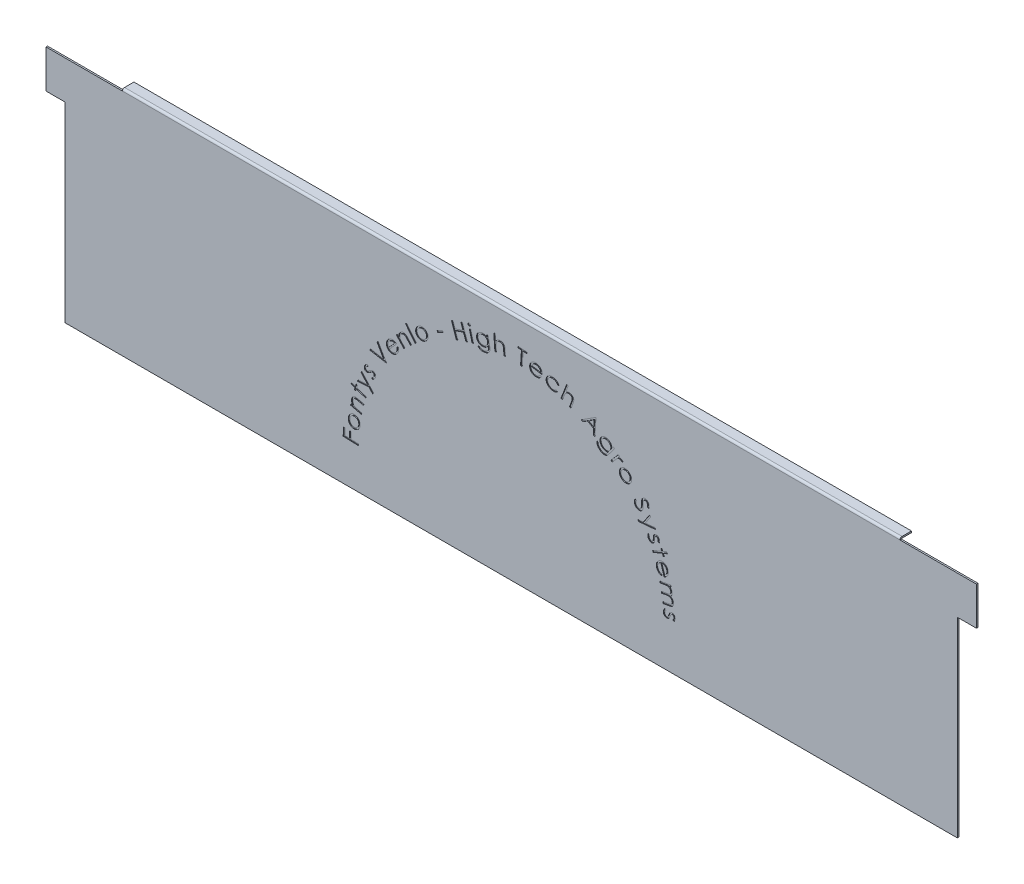
SolidWorks part; units mm, degrees
note: The reader was unsure of these and kept them because the rebuilt part matched: flange length of "Edge-Flange1".
material "1060 Alloy"
ref_plane "Front Plane" through (0, 0, 0) normal (0, 0, 1) x (1, 0, 0)
ref_plane "Top Plane" through (0, 0, 0) normal (0, 1, 0) x (1, 0, 0)
ref_plane "Right Plane" through (0, 0, 0) normal (1, 0, 0) x (0, 0, -1)
sketch "Sketch1" plane through (0, 0, 0) normal (0, 0, 1) x (1, 0, 0)
  line L0 (960.4168, 91.4559) -> (985.4168, 91.4559)
  line L1 (-231.5832, 141.4559) -> (985.4168, 141.4559)
  line L2 (-231.5832, 141.4559) -> (-231.5832, 91.4559)
  line L3 (-231.5832, 91.4559) -> (-206.5832, 91.4559)
  line L4 (985.4168, 141.4559) -> (985.4168, 91.4559)
  line L6 (-206.5832, 91.4559) -> (-206.5832, -158.5441)
  line L7 (-206.5832, -158.5441) -> (960.4168, -158.5441)
  line L8 (960.4168, 91.4559) -> (960.4168, -158.5441)
  dimension "D1" = 1217
  dimension "D2" = 50
  dimension "D3" = 250
  dimension "D4" = 25
  dimension "D5" = 25
base flange "Base-Flange1" sketch "Sketch1" thickness 2 reverse thickness direction no parameters "D1"=0.7366
edge flange "Edge-Flange1" sketch "Sketch5" flange angle 90 flange length 15 flange position bend outside bend radius 0.7366 thickness 2 relief rectangular parameters "D6"=10
sketch "Sketch5" plane through (0, 141.4559, -2) normal (0, 1, 0) x (1, 0, 0)
  line L2 (-131.5832, 0) -> (-131.5832, 13)
  line L3 (-131.5832, 13) -> (885.4168, 13)
  line L4 (885.4168, 13) -> (885.4168, 0)
  line L7 (985.4168, 0) -> (-231.5832, 0) construction
  line L8 (885.4168, 0) -> (-131.5832, 0)
  line L11 (-231.5832, 0) -> (-231.5832, -2) construction
  line L12 (985.4168, 0) -> (985.4168, -2) construction
  dimension "D1" = 100
  dimension "D2" = 100
bend "EdgeBend1" bend radius 0.7366 bend angle 90 parameters "D5"=1
sketch "Sketch6" plane through (0, 0, 0) normal (0, 0, 1) x (1, 0, 0)
  line L4 (885.4168, 141.4559) -> (-131.5832, 141.4559) construction
  line L5 (-206.5832, 91.4559) -> (-206.5832, -158.5441) construction
  arc A0 (176.9168, -108.5441) -> (576.9168, -108.5441) centre (376.9168, -108.5441) cw construction
  text T0 "Fontys Venlo - High Tech Agro Systems" font "Century Gothic" height 20
  dimension "D1" = 200
  dimension "D2" = 250
  dimension "D3" = 583.5
extrude "Cut-Extrude1" cut sketch "Sketch6" against normal blind 1
sketch "Bend-Lines1" plane through (0, 0, 0) normal (0, 1, 0) x (1, 0, 0)
sketch "Bounding-Box1" plane through (0, 0, 0) normal (0, 1, 0) x (1, 0, 0)
sheet metal parameters "Sheet-Metal1" thickness 2 parameters "D1"=0.7366
flat pattern "Flat-Pattern1"
sketch "Bend-Lines2" plane through (0, 0, 0) normal (0, 1, 0) x (1, 0, 0)
sketch3d "Bounding-Box2"
  line L0 (-231.5832, -108.5441, 0) -> (985.4168, -108.5441, 0) construction
  line L1 (-231.5832, 141.4559, 0) -> (985.4168, 141.4559, 0) construction
  line L2 (-231.5832, -108.5441, 0) -> (-231.5832, 141.4559, 0) construction
  line L3 (985.4168, -108.5441, 0) -> (985.4168, 141.4559, 0) construction
sheet metal parameters "Sheet-Metal2" thickness 2 parameters "D1"=0.7366
flat pattern "Flat-Pattern1"
sketch "Bend-Lines2" plane through (0, 0, 0) normal (0, 0, 1) x (1, 0, 0)
  line L0 (885.4168, 142.8198) -> (-131.5832, 142.8198) construction
  line L1 (885.4168, 142.8198) -> (-131.5832, 142.8198) construction
sketch3d "Bounding-Box2"
  line L0 (-231.5832, -158.5441, 0) -> (985.4168, -158.5441, 0) construction
  line L1 (-231.5832, 156.4471, 0) -> (985.4168, 156.4471, 0) construction
  line L2 (-231.5832, -158.5441, 0) -> (-231.5832, 156.4471, 0) construction
  line L3 (985.4168, -158.5441, 0) -> (985.4168, 156.4471, 0) construction
bend of the flat pattern "Flatten-<EdgeBend1>1"
sheet metal parameters "Sheet-Metal3" thickness 2 parameters "D1"=0.7366
flat pattern "Flat-Pattern1"
sketch "Bend-Lines2" plane through (0, 0, 0) normal (0, 0, 1) x (1, 0, 0)
  line L0 (885.4168, 142.8198) -> (-131.5832, 142.8198) construction
  line L1 (885.4168, 142.8198) -> (-131.5832, 142.8198) construction
sketch3d "Bounding-Box2"
  line L0 (-231.5832, -158.5441, 0) -> (985.4168, -158.5441, 0) construction
  line L1 (-231.5832, 156.4471, 0) -> (985.4168, 156.4471, 0) construction
  line L2 (-231.5832, -158.5441, 0) -> (-231.5832, 156.4471, 0) construction
  line L3 (985.4168, -158.5441, 0) -> (985.4168, 156.4471, 0) construction
bend of the flat pattern "Flatten-<EdgeBend1>2"
sheet metal parameters "Sheet-Metal4" thickness 2 parameters "D1"=0.7366
flat pattern "Flat-Pattern4"
sketch "Bend-Lines4" plane through (0, 0, 0) normal (0, 1, 0) x (1, 0, 0)
sketch3d "Bounding-Box4" [suppressed]
  line L0 (438.6533, 28.4061, 0) -> (443.5811, 24.4286, 0) construction
  line L1 (435.0553, 23.9484, 0) -> (439.983, 19.9709, 0) construction
  line L2 (438.6533, 28.4061, 0) -> (435.0553, 23.9484, 0) construction
  line L3 (443.5811, 24.4286, 0) -> (439.983, 19.9709, 0) construction
sheet metal parameters "Sheet-Metal5" thickness 2 parameters "D1"=0.7366
flat pattern "Flat-Pattern5"
sketch "Bend-Lines5" plane through (0, 0, 0) normal (0, 1, 0) x (1, 0, 0)
sketch3d "Bounding-Box5" [suppressed]
  line L0 (452.0841, 17.1021, 0) -> (456.1995, 12.4271, 0) construction
  line L1 (447.6628, 13.21, 0) -> (451.7782, 8.5351, 0) construction
  line L2 (452.0841, 17.1021, 0) -> (447.6628, 13.21, 0) construction
  line L3 (456.1995, 12.4271, 0) -> (451.7782, 8.5351, 0) construction
sheet metal parameters "Sheet-Metal6" thickness 2 parameters "D1"=0.7366
flat pattern "Flat-Pattern6"
sketch "Bend-Lines6" plane through (0, 0, 0) normal (0, 1, 0) x (1, 0, 0)
sketch3d "Bounding-Box6" [suppressed]
  line L0 (317.825, 22.7921, 0) -> (322.7823, 26.5097, 0) construction
  line L1 (314.2735, 27.528, 0) -> (319.2308, 31.2456, 0) construction
  line L2 (317.825, 22.7921, 0) -> (314.2735, 27.528, 0) construction
  line L3 (322.7823, 26.5097, 0) -> (319.2308, 31.2456, 0) construction
sheet metal parameters "Sheet-Metal7" thickness 2 parameters "D1"=0.7366
flat pattern "Flat-Pattern7"
sketch "Bend-Lines7" plane through (0, 0, 0) normal (0, 1, 0) x (1, 0, 0)
sketch3d "Bounding-Box7" [suppressed]
  line L0 (276.6653, -48.5354, 0) -> (277.7535, -42.4183, 0) construction
  line L1 (270.8472, -47.5004, 0) -> (271.9355, -41.3833, 0) construction
  line L2 (276.6653, -48.5354, 0) -> (270.8472, -47.5004, 0) construction
  line L3 (277.7535, -42.4183, 0) -> (271.9355, -41.3833, 0) construction
sheet metal parameters "Sheet-Metal8" thickness 2 parameters "D1"=0.7366
flat pattern "Flat-Pattern8"
sketch "Bend-Lines8" plane through (0, 0, 0) normal (0, 1, 0) x (1, 0, 0)
sketch3d "Bounding-Box8" [suppressed]
  line L0 (356.1736, 39.999, 0) -> (362.3149, 41.318, 0) construction
  line L1 (354.9724, 45.5918, 0) -> (361.1136, 46.9109, 0) construction
  line L2 (356.1736, 39.999, 0) -> (354.9724, 45.5918, 0) construction
  line L3 (362.3149, 41.318, 0) -> (361.1136, 46.9109, 0) construction
sheet metal parameters "Sheet-Metal9" thickness 2 parameters "D1"=0.7366
flat pattern "Flat-Pattern9"
sketch "Bend-Lines9" plane through (0, 0, 0) normal (0, 1, 0) x (1, 0, 0)
sketch3d "Bounding-Box9" [suppressed]
  line L0 (296.881, 8.3602, 0) -> (300.8694, 12.7732, 0) construction
  line L1 (295.2387, 9.8445, 0) -> (299.227, 14.2575, 0) construction
  line L2 (296.881, 8.3602, 0) -> (295.2387, 9.8445, 0) construction
  line L3 (300.8694, 12.7732, 0) -> (299.227, 14.2575, 0) construction
sheet metal parameters "Sheet-Metal10" thickness 2 parameters "D1"=0.7366
flat pattern "Flat-Pattern10"
sketch "Bend-Lines10" plane through (0, 0, 0) normal (0, 1, 0) x (1, 0, 0)
sketch3d "Bounding-Box10" [suppressed]
  line L0 (477.7975, -24.2481, 0) -> (479.5543, -29.9272, 0) construction
  line L1 (475.6824, -24.9024, 0) -> (477.4392, -30.5815, 0) construction
  line L2 (477.7975, -24.2481, 0) -> (475.6824, -24.9024, 0) construction
  line L3 (479.5543, -29.9272, 0) -> (477.4392, -30.5815, 0) construction
sheet metal parameters "Sheet-Metal11" thickness 2 parameters "D1"=0.7366
flat pattern "Flat-Pattern11"
sketch "Bend-Lines11" plane through (0, 0, 0) normal (0, 1, 0) x (1, 0, 0)
sketch3d "Bounding-Box11" [suppressed]
  line L0 (390.8617, 47.1238, 0) -> (396.7431, 46.1803, 0) construction
  line L1 (390.5092, 44.9268, 0) -> (396.3906, 43.9833, 0) construction
  line L2 (390.8617, 47.1238, 0) -> (390.5092, 44.9268, 0) construction
  line L3 (396.7431, 46.1803, 0) -> (396.3906, 43.9833, 0) construction
sheet metal parameters "Sheet-Metal12" thickness 2 parameters "D1"=0.7366
flat pattern "Flat-Pattern12"
sketch "Bend-Lines12" plane through (0, 0, 0) normal (0, 1, 0) x (1, 0, 0)
sketch3d "Bounding-Box12" [suppressed]
  line L0 (429.8572, 29.3125, 0) -> (433.2827, 31.474, 0) construction
  line L1 (428.1075, 32.0855, 0) -> (431.533, 34.2469, 0) construction
  line L2 (429.8572, 29.3125, 0) -> (428.1075, 32.0855, 0) construction
  line L3 (433.2827, 31.474, 0) -> (431.533, 34.2469, 0) construction
